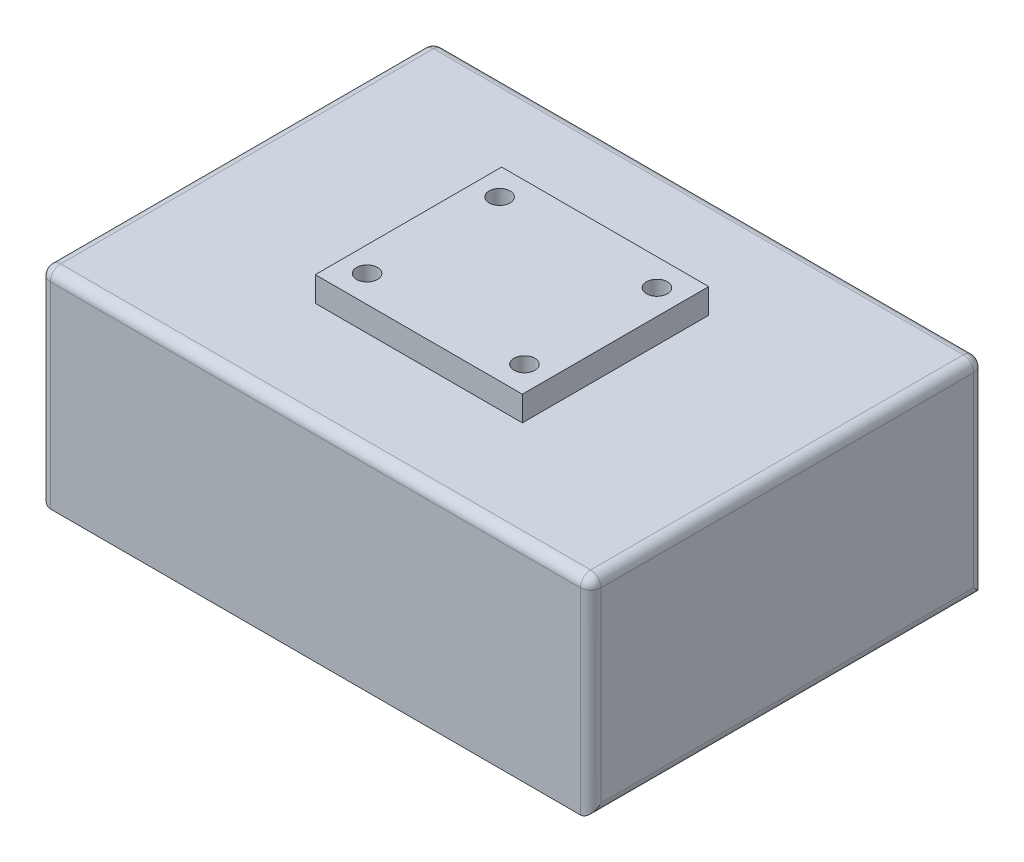
SolidWorks part; units mm, degrees
ref_plane "Front Plane" through (0, 0, 0) normal (0, 0, 1) x (1, 0, 0)
ref_plane "Top Plane" through (0, 0, 0) normal (0, 1, 0) x (1, 0, 0)
ref_plane "Right Plane" through (0, 0, 0) normal (1, 0, 0) x (0, 0, -1)
sketch "Sketch1" plane through (0, 0, 0) normal (0, 1, 0) x (1, 0, 0)
  line L1 (0, 0) -> (133, 0)
  line L2 (0, 0) -> (0, 95)
  line L3 (0, 95) -> (133, 95)
  line L4 (133, 0) -> (133, 95)
  dimension "D1" = 95
  dimension "D2" = 133
extrude "Boss-Extrude1" add sketch "Sketch1" along normal blind 50
sketch "Sketch2" plane through (0, 0, 0) normal (-1, 0, 0) x (0, 0, 1)
  line L0 (-95, 0) -> (0, 0) construction
  line L1 (-94, 0) -> (-1, 0)
  arc A0 (-1, 0) -> (-94, 0) centre (-47.5, 0) ccw
  dimension "D1" = 93
extrude "Cut-Extrude1" cut sketch "Sketch2" against normal offset from surface (129 mm away) 2 from offset 2 up to face at (133, 25, -47.5) offset against normal yes
sketch "Sketch3" plane through (0, 0, 0) normal (-1, 0, 0) x (0, 0, 1)
  line L0 (-95, 0) -> (0, 0) construction
  circle A0 centre (-47.5, 0) radius 42.5
  dimension "D1" = 85
extrude "Cut-Extrude2" cut sketch "Sketch3" against normal blind 10
fillet "Fillet1" radius 2.5 12 edges at (66.5, 50, -95) (133, 50, -47.5) (66.5, 50, 0) (0, 50, -47.5) (133, 25, 0) (133, 25, -95) (133, 0, -47.5) (0, 25, -95) (0, 25, 0) (0, 0, -2.5) (0, 42.5, -47.5) (0, 0, -92.5)
sketch "Sketch4" plane through (0, 50, 0) normal (0, 1, 0) x (1, 0, 0)
  line L0 (2.5, 92.5) -> (130.5, 2.5) construction
  line L1 (2.5, 2.5) -> (130.5, 92.5) construction
  line L3 (41.5, 70) -> (91.5, 70)
  line L4 (41.5, 70) -> (41.5, 25)
  line L5 (41.5, 25) -> (91.5, 25)
  line L6 (91.5, 70) -> (91.5, 25)
  line L7 (41.5, 70) -> (91.5, 25) construction
  line L8 (41.5, 25) -> (91.5, 70) construction
  point P8 (66.5, 47.5)
  dimension "D1" = 50
  dimension "D2" = 45
extrude "Boss-Extrude2" add sketch "Sketch4" along normal blind 6
sketch "Sketch5" plane through (0, 56, 0) normal (0, 1, 0) x (1, 0, 0)
  line L0 (41.5, 70) -> (41.5, 25) construction
  line L1 (91.5, 70) -> (41.5, 70) construction
  line L3 (91.5, 25) -> (91.5, 70) construction
  line L5 (41.5, 25) -> (91.5, 25) construction
  circle A0 centre (47.5, 63.5) radius 2.525
  circle A1 centre (85.5, 63.5) radius 2.525
  circle A2 centre (85.5, 31.5) radius 2.525
  circle A3 centre (47.5, 31.5) radius 2.525
  point P10 (41.5, 47.5)
  point P13 (66.5, 70)
  point P16 (91.5, 47.5)
  point P19 (66.5, 25)
  dimension "D1" = 5.05
  dimension "D2" = 5.05
  dimension "D9" = 5.05
  dimension "D10" = 5.05
  dimension "D3" = 16
  dimension "D4" = 19
  dimension "D5" = 19
  dimension "D6" = 16
  dimension "D7" = 16
  dimension "D8" = 19
  dimension "D11" = 19
  dimension "D12" = 16
extrude "Cut-Extrude3" cut sketch "Sketch5" against normal blind 4
